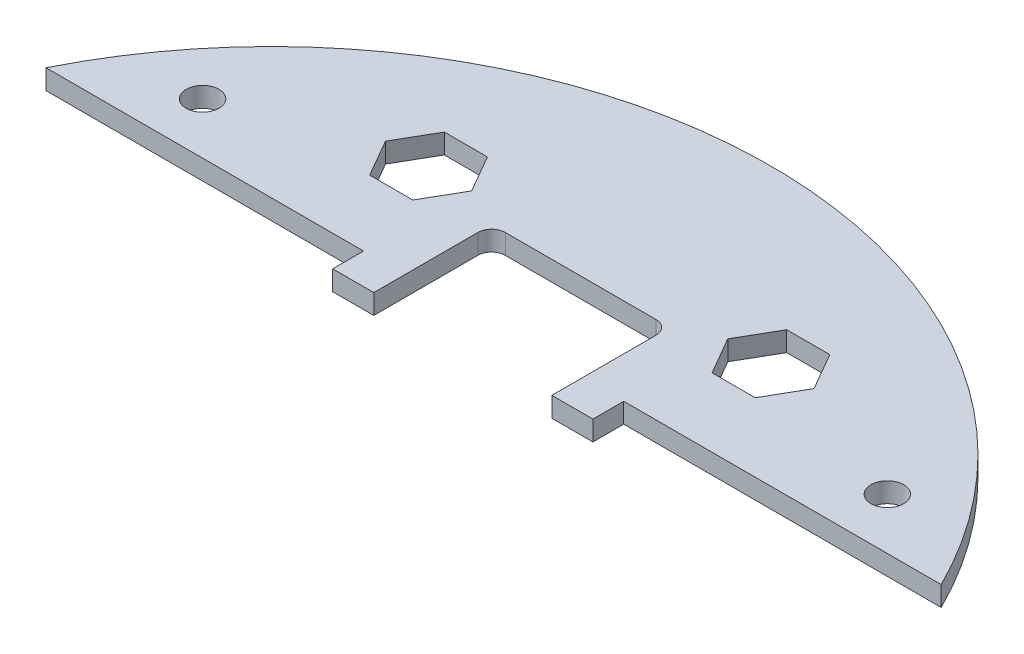
SolidWorks part; units mm, degrees
material "Acrylic (Medium-high impact)"
ref_plane "Front Plane" through (0, 0, 0) normal (0, 0, 1) x (1, 0, 0)
ref_plane "Top Plane" through (0, 0, 0) normal (0, 1, 0) x (1, 0, 0)
ref_plane "Right Plane" through (0, 0, 0) normal (1, 0, 0) x (0, 0, -1)
sketch "Sketch1" plane through (0, 0, 0) normal (0, 1, 0) x (1, 0, 0)
  line L0 (0, -85) -> (-32.7511, -65.2408) construction
  line L1 (0, -85) -> (0, 0) construction
  arc A0 (36.8566, -63.0126) -> (-36.8566, -63.0126) centre (0, 0) ccw
  arc A1 (30.3631, -61.7375) -> (-30.3631, -61.7375) centre (0, -85) ccw
  arc A2 (36.8566, -63.0126) -> (30.3631, -61.7375) centre (34.3322, -58.6967) cw
  arc A3 (-30.3631, -61.7375) -> (-36.8566, -63.0126) centre (-34.3322, -58.6967) cw
  dimension "D1" = 146
  dimension "D2" = 76.5
  dimension "D4" = 5
  dimension "D3" = 85
extrude "Boss-Extrude1" add sketch "Sketch1" along normal blind 2.9
sketch "solenoid placement" plane through (0, 2.9, 0) normal (0, 1, 0) x (1, 0, 0)
  line L4 (-19, -36) -> (19, -36)
  line L5 (-19, 28) -> (-19, -36)
  line L6 (19, 28) -> (-19, 28)
  line L7 (19, -36) -> (19, 28)
  line L8 (-19, -36) -> (19, -36)
  line L9 (-19, 28) -> (-19, -36)
  line L10 (19, 28) -> (-19, 28)
  line L11 (19, -36) -> (19, 28)
  dimension "D1" = 0
extrude "Cut-Extrude1" cut sketch "solenoid placement" against normal through all
sketch "Sketch4" plane through (0, 2.9, 0) normal (0, 1, 0) x (1, 0, 0)
  line L6 (-13, 28) -> (13, 28)
  line L7 (13, 28) -> (13, 43.2)
  line L8 (11, 45.2) -> (-11, 45.2)
  line L9 (-13, 43.2) -> (-13, 28)
  line L10 (-13, 28) -> (13, 28)
  line L11 (13, 28) -> (13, 43.2)
  line L12 (11, 45.2) -> (-11, 45.2)
  line L13 (-13, 43.2) -> (-13, 28)
  arc A4 (13, 43.2) -> (11, 45.2) centre (11, 43.2) ccw
  arc A5 (13, 43.2) -> (11, 45.2) centre (11, 43.2) ccw
  arc A6 (-11, 45.2) -> (-13, 43.2) centre (-11, 43.2) ccw
  arc A7 (-11, 45.2) -> (-13, 43.2) centre (-11, 43.2) ccw
  dimension "D1" = 0
extrude "Cut-Extrude4" cut sketch "Sketch4" against normal through all
sketch "Sketch5" plane through (0, 2.9, 0) normal (0, 1, 0) x (1, 0, 0)
  line L0 (0, 0) -> (0, 73) construction
  line L1 (-18.7069, 48) -> (-21.8534, 53.45)
  line L2 (-21.8534, 53.45) -> (-28.1466, 53.45)
  line L3 (-28.1466, 53.45) -> (-31.2931, 48)
  line L4 (-31.2931, 48) -> (-28.1466, 42.55)
  line L5 (-28.1466, 42.55) -> (-21.8534, 42.55)
  line L6 (-21.8534, 42.55) -> (-18.7069, 48)
  line L7 (21.8534, 42.55) -> (18.7069, 48)
  line L8 (28.1466, 42.55) -> (21.8534, 42.55)
  line L9 (31.2931, 48) -> (28.1466, 42.55)
  line L10 (28.1466, 53.45) -> (31.2931, 48)
  line L11 (21.8534, 53.45) -> (28.1466, 53.45)
  line L12 (18.7069, 48) -> (21.8534, 53.45)
  circle A0 centre (-25, 48) radius 5.45 construction
  circle A2 centre (25, 48) radius 5.45 construction
  arc A3 (36.8566, -63.0126) -> (-36.8566, -63.0126) centre (0, 0) ccw construction
  dimension "D3" = 10.9
extrude "Cut-Extrude5" cut sketch "Sketch5" against normal through all
sketch "Sketch6" plane through (0, 2.9, 0) normal (0, 1, 0) x (1, 0, 0)
  circle A1 centre (40, -40) radius 2.4
  circle A2 centre (40, -40) radius 2.4
  circle A3 centre (-40, -40) radius 2.4
  circle A4 centre (-40, -40) radius 2.4
  circle A5 centre (-50, 40) radius 2.4
  circle A6 centre (-50, 40) radius 2.4
  circle A7 centre (50, 40) radius 2.4
  circle A8 centre (50, 40) radius 2.4
  dimension "D1" = 0
  dimension "D2" = 0
  dimension "D3" = 0
  dimension "D4" = 0
extrude "Cut-Extrude6" cut sketch "Sketch6" against normal through all
sketch "Sketch3" plane through (0, 2.9, 0) normal (0, 1, 0) x (1, 0, 0)
  line L0 (-19, 28) -> (19, 28)
  line L1 (-73, -32.5) -> (73, -32.5)
  line L2 (-73, -32.5) -> (-73, 32.5)
  line L3 (-73, 32.5) -> (-19, 32.5)
  line L4 (73, -32.5) -> (73, 32.5)
  line L5 (-73, -32.5) -> (73, 32.5) construction
  line L6 (-73, 32.5) -> (73, -32.5) construction
  line L7 (19, 28) -> (19, 32.5)
  line L8 (-19, 28) -> (-19, 32.5)
  line L9 (19, 32.5) -> (73, 32.5)
  arc A0 (36.8566, -63.0126) -> (-36.8566, -63.0126) centre (0, 0) ccw construction
  point P0 (0, 0)
  dimension "D1" = 65
extrude "Cut-Extrude3" cut sketch "Sketch3" against normal through all
sketch "Sketch7" plane through (0, 2.9, 0) normal (0, 1, 0) x (1, 0, 0)
  line L4 (5, 0) -> (-5, 0)
  line L5 (5, -62.8025) -> (5, 0)
  line L6 (-5, -62.8025) -> (5, -62.8025)
  line L7 (-5, 0) -> (-5, -62.8025)
  line L8 (5, 0) -> (-5, 0)
  line L9 (5, -62.8025) -> (5, 0)
  line L10 (-5, -62.8025) -> (5, -62.8025)
  line L11 (-5, 0) -> (-5, -62.8025)
  dimension "D1" = 0
extrude "Cut-Extrude7" cut sketch "Sketch7" against normal through all
delete or keep bodies "Body-Delete/Keep 1" type delete bodies bodies 116 117
equation "\"smallPulleyTeeth\"= 15"
equation "\"largePulleyTeeth\"= 30"
equation "\"eighthThick\"= 2.9mm"
equation "\"sixteenthThick\" = 1.7mm"
equation "\"quarterThick\"=6.0mm"
equation "\"OD\" = 146mm"
equation "\"puckAngle\" = 60.5deg"
equation "\"D1@Sketch1\"=\"OD\""
equation "\"puckDiam\" = 76.5mm"
equation "\"D2@Sketch1\"=\"puckDiam\""
equation "\"D1@Boss-Extrude1\"=\"eighthThick\""
equation "\"axlePress\" = 5.9mm"
equation "\"press\" = 0.2mm"
equation "\"wheelClear\" = 0.3mm"
equation "\"10-32clear\" = 4.8mm"
equation "\"6-32clear\" = 3.3mm"
equation "\"8-32clear\" = 4.0mm"
equation "\"wheelHeight\" = 22mm"
equation "\"wheelWell\" = 65mm"
equation "\"D1@Sketch3\"=\"wheelWell\""
equation "\"puckDist\" = 85mm"
equation "\"scoopFillet\" = 5mm"
equation "\"4-40clear\" = 3.0mm"
equation "\"D3@Sketch1\"=\"puckDist\""
equation "\"D4@Sketch1\"=\"scoopFillet\""
